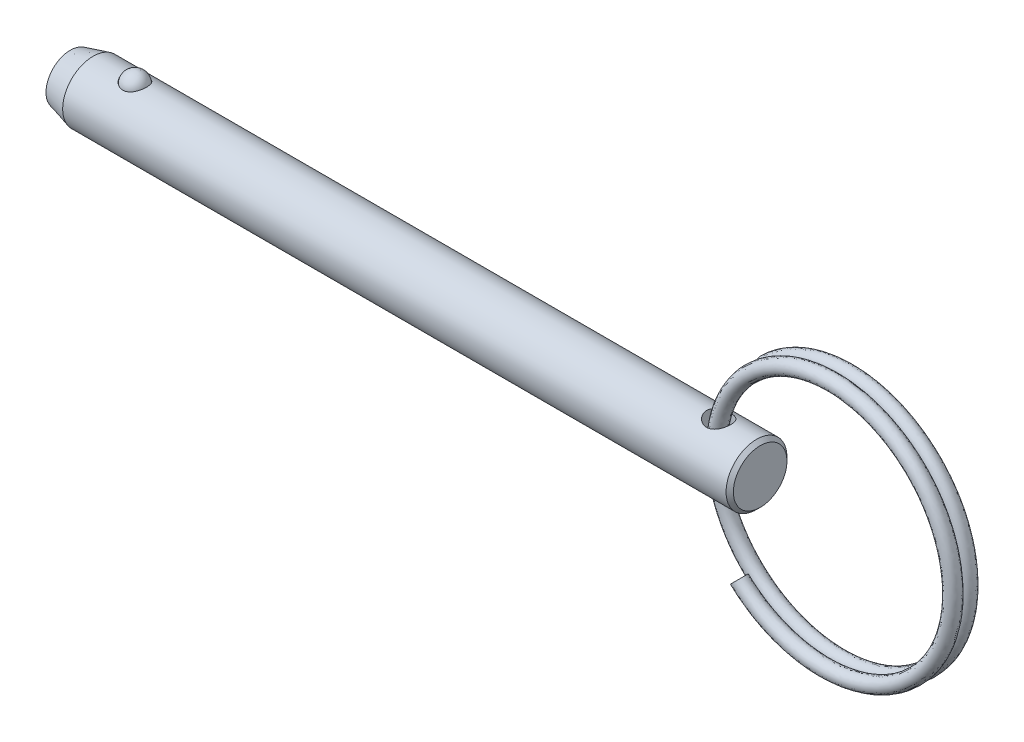
SolidWorks part; units mm, degrees
ref_plane "Front" through (0, 0, 0) normal (0, 0, 1) x (1, 0, 0)
ref_plane "Top" through (0, 0, 0) normal (0, 1, 0) x (1, 0, 0)
ref_plane "Right" through (0, 0, 0) normal (1, 0, 0) x (0, 0, -1)
sketch "Sketch1" plane through (0, 0, 0) normal (0, 0, 1) x (1, 0, 0)
  line L0 (35.9664, 2.794) -> (35.5854, 3.175)
  line L1 (35.5854, 3.175) -> (35.9664, 3.175) construction
  line L4 (35.9664, 2.794) -> (35.9664, 0)
  line L5 (35.9664, 3.175) -> (35.9664, 2.794) construction
  line L16 (35.5854, 3.175) -> (-33.5965, 3.175)
  line L17 (-35.9664, 3.175) -> (-35.9664, 2.54) construction
  line L19 (-33.5965, 3.175) -> (-35.9664, 3.175) construction
  line L22 (-35.9664, -3.175) -> (-33.5965, -3.175) construction
  line L23 (-29.2319, 2.8575) -> (-29.2319, -2.8575) construction
  line L24 (-35.9664, 0) -> (35.9664, 0)
  line L27 (35.9664, 0) -> (38.7604, 0) construction
  line L29 (-35.9664, 0) -> (-35.9664, -2.54) construction
  line L36 (30.3784, 0) -> (30.3784, 3.175) construction
  line L37 (-35.9664, 2.54) -> (-35.9664, 0)
  line L38 (-33.5965, -3.175) -> (35.9664, -3.175) construction
  line L39 (-35.9664, -2.54) -> (-35.9664, -3.175) construction
  line L40 (-33.5965, 3.175) -> (-35.9664, 2.54)
  line L42 (-33.5965, -3.175) -> (-35.9664, -2.54) construction
  line L43 (-33.5965, 3.175) -> (-33.5965, -3.175) construction
  circle A2 centre (-29.2319, 2.8575) radius 1.2319 construction
  point P35 (-28.0416, 3.175)
  dimension "A1" = 15
revolve "Revolve1" add sketch "Sketch1" angle 360 about L27
sketch "Sketch2" plane through (0, 0, 0) normal (0, 0, 1) x (1, 0, 0)
  line L0 (-27.9746, 2.8575) -> (-30.4892, 2.8575)
  line L1 (-29.2319, 4.0894) -> (-29.2319, 4.1148) construction
  line L2 (-27.9746, 2.8575) -> (-25.46, 2.8575) construction
  circle A0 centre (-29.2319, 2.8575) radius 1.2319 construction
  circle A1 centre (-29.2319, 2.8575) radius 1.2319 construction
  arc A2 (-30.4892, 2.8575) -> (-27.9746, 2.8575) centre (-29.2319, 2.8575) cw
  dimension "D1" = 0.0254
revolve "Cut-Revolve1" cut sketch "Sketch2" angle 360 about L2
sketch "Sketch3" plane through (0, 0, 0) normal (0, 0, 1) x (1, 0, 0)
  line L0 (-28, 2.8575) -> (-30.4638, 2.8575)
  line L1 (-28, 2.8575) -> (-25.5362, 2.8575) construction
  circle A0 centre (-29.2319, 2.8575) radius 1.2319 construction
  arc A1 (-28, 2.8575) -> (-30.4638, 2.8575) centre (-29.2319, 2.8575) ccw
revolve "Revolve2" add sketch "Sketch3" angle 360 about L1
sketch "Sketch4" plane through (0, 0, 0) normal (0, 0, 1) x (1, 0, 0)
  line L1 (31.6484, -3.175) -> (32.9184, -3.175)
  line L2 (31.6484, -3.175) -> (31.6484, 3.175)
  line L3 (31.6484, 3.175) -> (32.9184, 3.175)
  line L4 (32.9184, -3.175) -> (32.9184, 3.175)
  line L5 (31.6484, -3.175) -> (31.6484, -4.445) construction
  line L6 (32.9184, 3.175) -> (35.9664, 3.175) construction
  line L8 (30.3784, -3.175) -> (30.3784, 3.175) construction
  line L9 (30.3784, 0) -> (31.6484, 0) construction
  line L11 (31.6484, 0) -> (32.9184, 0) construction
  line L12 (35.5854, 3.175) -> (-33.5965, 3.175) construction
  line L14 (-33.5965, -3.175) -> (35.9664, -3.175) construction
revolve "Cut-Revolve2" cut sketch "Sketch4" angle 360 about L2
sketch "Sketch5" plane through (0, 0, 0) normal (0, 0, 1) x (1, 0, 0)
  line L0 (0, 0) -> (30.6714, 0) construction
  line L1 (30.6714, 0) -> (30.6714, 3.175) construction
  line L2 (35.5854, 3.175) -> (-33.5965, 3.175) construction
  line L3 (44.1334, 0) -> (57.5954, 0) construction
  line L4 (32.9184, 3.175) -> (32.6254, 3.175) construction
  line L5 (31.6484, 3.175) -> (32.9184, 3.175) construction
  line L6 (31.0512, 3.175) -> (31.0512, -3.175) construction
  line L7 (30.6714, 3.175) -> (30.3784, 3.175) construction
  line L8 (31.6484, -3.175) -> (32.9184, -3.175) construction
  line L9 (31.0512, -3.175) -> (32.9184, -3.175) construction
  line L10 (30.6714, 0) -> (44.1334, 0) construction
  line L12 (32.6254, 3.175) -> (31.0512, 3.175) construction
  line L13 (44.1334, 11.938) -> (44.1334, 13.462) construction
  circle A0 centre (44.1334, 0) radius 13.462
  circle A1 centre (44.1334, 0) radius 11.938 construction
  circle A2 centre (44.1334, 0) radius 12.7 construction
  point P26 (44.1334, 12.7)
curve "Helix/Spiral1" pitch 1.5494 height 1.3557 radius 13.462 left hand yes centre (44.1334, 0, 0) axis (0, 0, -1) start towards (1, 0, 0)
sketch "Sketch6" plane through (114.0038, 0, 0) normal (0, 1, 0) x (0, 0, -1)
  line L0 (0, 81.8084) -> (0, 82.5704) construction
  line L1 (0, 82.5704) -> (0, 83.3324) construction
  circle A0 centre (0, 82.5704) radius 0.762
  dimension "D1" = 1.524
sketch "Sketch7" plane through (0, 0, 0) normal (0, 0, 1) x (1, 0, 0)
  circle A0 centre (44.1334, 0) radius 13.462 construction
  circle A1 centre (44.1334, 0) radius 13.462
curve "Helix/Spiral2" pitch 1.5494 height 1.3557 radius 13.462 left hand yes centre (44.1334, 0, 0) axis (0, 0, 1) start towards (1, 0, 0)
sweep "Sweep1" add profiles "Sketch6" path "Helix/Spiral1"
sweep "Sweep2" add profiles "Sketch6<2>" path "Helix/Spiral2"
sketch "Sketch6<2>" plane through (114.0038, 0, 0) normal (0, 1, 0) x (0, 0, -1) same geometry as "Sketch6"
equation "\"D12@Sketch1\"=\"A@Sketch1\" * 0.80"
equation "\"D2@Sketch1\"=\"A@Sketch1\" * 0.9"
equation "\"D1@Sketch4\" = \"A@Sketch1\" / 2.5"
equation "\"Ring OD@Sketch5\" = \"R Ring Dia@Sketch5\" * 0.06"
equation "\"D4@Helix/Spiral1\"=\"Ring OD@Sketch5\" + 0.001"
equation "\"D1@Sketch6\"=\"Ring OD@Sketch5\""
equation "\"D4@Helix/Spiral2\" = \"D4@Helix/Spiral1\""
equation "\"D5@Helix/Spiral2\" = \"D5@Helix/Spiral1\""
